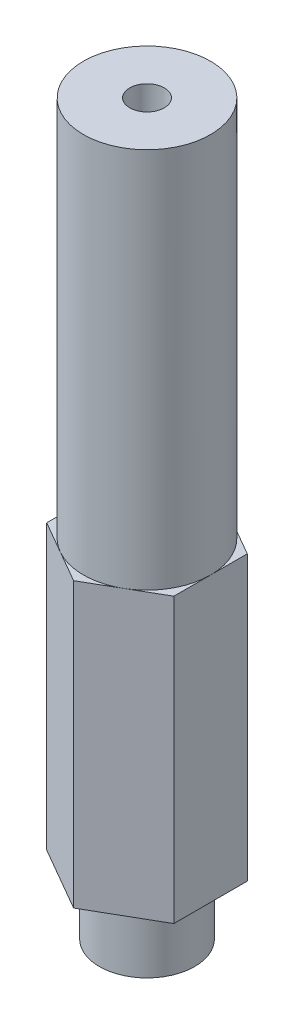
SolidWorks part; units mm, degrees
material "7075-T6 (SN)"
ref_plane "Front Plane" through (0, 0, 0) normal (0, 0, 1) x (1, 0, 0)
ref_plane "Top Plane" through (0, 0, 0) normal (0, 1, 0) x (1, 0, 0)
ref_plane "Right Plane" through (0, 0, 0) normal (1, 0, 0) x (0, 0, -1)
sketch "Sketch1" plane through (0, 0, 0) normal (0, 1, 0) x (1, 0, 0)
  line L1 (6.35, -3.6662) -> (6.35, 3.6662)
  line L2 (6.35, 3.6662) -> (0, 7.3323)
  line L3 (0, 7.3323) -> (-6.35, 3.6662)
  line L4 (-6.35, 3.6662) -> (-6.35, -3.6662)
  line L5 (-6.35, -3.6662) -> (0, -7.3323)
  line L6 (0, -7.3323) -> (6.35, -3.6662)
  circle A0 centre (0, 0) radius 6.35 construction
  dimension "D1" = 12.7
extrude "Boss-Extrude1" add sketch "Sketch1" along normal blind 28.321
sketch "Sketch2" plane through (0, 0, 0) normal (0, -1, 0) x (1, 0, 0)
  circle A0 centre (0, 0) radius 4.7625
  dimension "D1" = 9.525
extrude "Boss-Extrude2" add sketch "Sketch2" along normal blind 6.35
sketch "Sketch3" plane through (0, 28.321, 0) normal (0, 1, 0) x (1, 0, 0)
  circle A0 centre (0, 0) radius 6.35
  dimension "D1" = 12.7
extrude "Boss-Extrude3" add sketch "Sketch3" along normal blind 38.1
sketch "Sketch4" plane through (0, 66.421, 0) normal (0, 1, 0) x (1, 0, 0)
  line L0 (-5.08, 3.81) -> (5.08, 3.81)
  circle A0 centre (0, 0) radius 6.35 construction
  arc A1 (5.08, 3.81) -> (-5.08, 3.81) centre (0, 0) ccw
  dimension "D1" = 3.81
extrude "Cut-Extrude1" [suppressed] cut sketch "Sketch4" against normal blind 25.4
ref_axis "Axis1" through (0, 66.421, 0) along (0, -1, 0)
hole_wizard "#8-32 Tapped Hole1" positions "Sketch5" profile "Sketch6" tap size "#8-32" standard "ANSI Inch"
sketch "Sketch5" plane through (0, 66.421, 0) normal (0, 1, 0) x (1, 0, 0)
  point P0 (0, 0)
sketch "Sketch6" plane through (0, 66.421, 0) normal (1, 0, 0) x (0, 0, 1)
  line L0 (0, 0) -> (0, 11.7058)
  line L1 (0, 11.7058) -> (1.7272, 10.668)
  line L2 (1.7272, 10.668) -> (1.7272, 0)
  line L5 (1.7272, 0) -> (0, 0)
  line L10 (0, 11.7058) -> (-1.7272, 10.668) construction
  line L11 (0, -6.35) -> (0, 107.95) construction
  dimension "Tap Drill Dia." = 3.4544
  dimension "Tap Drill Depth" = 10.668
  dimension "Drill Angle" = 118
cosmetic thread "Hole Thread1" parameters "D1"=8.382, "D2"=4.1656
sketch "Sketch7" plane through (0, -6.35, 0) normal (0, -1, 0) x (1, 0, 0)
  circle A0 centre (0, 0) radius 3.175
  dimension "D1" = 6.35
extrude "Cut-Extrude2" cut sketch "Sketch7" against normal blind 6.35 contours A0
sketch "Sketch8" plane through (0, 66.421, 0) normal (0, 1, 0) x (1, 0, 0)
  line L1 (-0.7938, 6.35) -> (0.7937, 6.35)
  line L2 (-3.9688, 3.175) -> (-3.9688, -3.175)
  line L3 (-0.7938, -6.35) -> (0.7937, -6.35)
  line L4 (3.9687, 3.175) -> (3.9687, -3.175)
  line L5 (-3.9688, 6.35) -> (3.9687, -6.35) construction
  line L6 (-3.9688, -6.35) -> (3.9687, 6.35) construction
  arc A0 (-3.9688, 3.175) -> (-0.7938, 6.35) centre (-0.7938, 3.175) cw
  arc A1 (0.7937, 6.35) -> (3.9687, 3.175) centre (0.7937, 3.175) cw
  arc A2 (3.9687, -3.175) -> (0.7937, -6.35) centre (0.7937, -3.175) cw
  arc A3 (-0.7938, -6.35) -> (-3.9688, -3.175) centre (-0.7938, -3.175) cw
  arc A4 (3.175, 5.4993) -> (-3.175, 5.4993) centre (0, 0) ccw construction
  circle A5 centre (0, 0) radius 6.35 construction
  circle A6 centre (0, 0) radius 6.35
  point P0 (0, 0)
  circle M6 centre (0, 0) radius 6.35
  dimension "D2" = 3.175
  dimension "D1" = 7.9375
extrude "Cut-Extrude3" [suppressed] cut sketch "Sketch8" against normal blind 12.7 contours A3 L2 A0 M6 | L4 A2 A1 M6
fillet "Fillet1" [suppressed] radius 0.381
